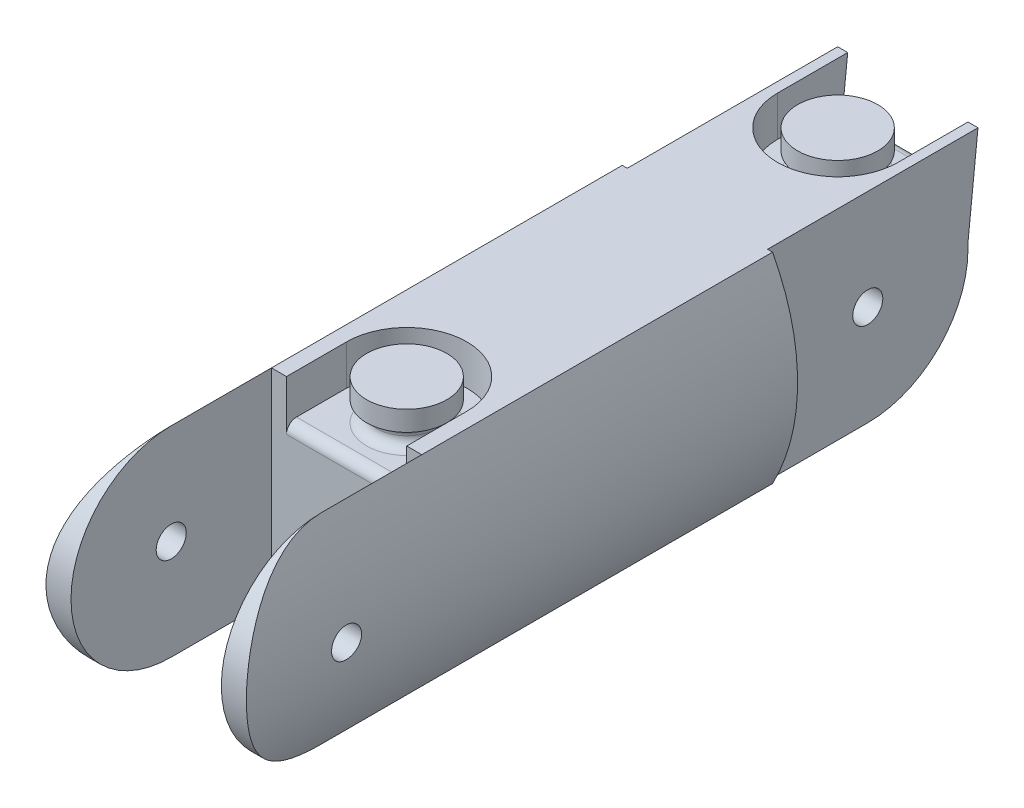
SolidWorks part; units mm, degrees
ref_plane "Alzado" through (0, 0, 0) normal (0, 0, 1) x (1, 0, 0)
ref_plane "Planta" through (0, 0, 0) normal (0, 1, 0) x (1, 0, 0)
ref_plane "Vista lateral" through (0, 0, 0) normal (1, 0, 0) x (0, 0, -1)
sketch "Croquis2" plane through (0, 0, 0) normal (0, 0, 1) x (1, 0, 0)
  line L5 (-7.5, -10) -> (7.5, -10)
  line L7 (-7.5, 10) -> (7.5, 10)
  line L9 (-7.5, -10) -> (7.5, 10) construction
  line L10 (-7.5, 10) -> (7.5, -10) construction
  arc A2 (-7.5, 10) -> (-7.5, -10) centre (11.25, 0) ccw
  arc A3 (7.5, -10) -> (7.5, 10) centre (-11.25, 0) ccw
  point P0 (0, 0)
  dimension "D1" = 15
  dimension "D2" = 20
extrude "Saliente-Extruir2" add sketch "Croquis2" along normal blind 55
sketch "Croquis4" plane through (0, 0, 0) normal (0, 0, -1) x (-1, 0, 0)
  line L1 (7.5, -10) -> (-7.5, -10) construction
  circle A0 centre (0, -7) radius 1.5
  dimension "D2" = 3
  dimension "D1" = 3
extrude "Cortar-Extruir1" cut sketch "Croquis4" against normal blind 50
sketch "Croquis3" plane through (0, 0, 0) normal (0, 0, -1) x (-1, 0, 0)
  line L8 (7.5, -10) -> (-7.5, -10) construction
  line L10 (7, 10) -> (7, -10)
  line L11 (7, -10) -> (3, -10)
  line L12 (-7, 10) -> (-7, -10)
  line L13 (7, 10) -> (-7, -10) construction
  line L14 (7, -10) -> (-7, 10) construction
  line L16 (3, -3) -> (3, -10)
  line L17 (-3, -10) -> (-7, -10)
  line L19 (-3, -3) -> (3, -3)
  line L20 (-3, -3) -> (-3, -10)
  line L21 (-7, 10) -> (7, 10)
  point P0 (0, 0)
  dimension "D1" = 14
  dimension "D2" = 4
  dimension "D3" = 4
  dimension "D4" = 7
extrude "Saliente-Extruir3" add sketch "Croquis3" along normal blind 20
sketch "Croquis8" plane through (-7, 0, 0) normal (-1, 0, 0) x (0, 0, 1)
  line L0 (-20, -10) -> (-20, 10) construction
  line L1 (-20, -10) -> (0, -10) construction
  circle A0 centre (-10, 0) radius 1.5
  point P4 (-20, 0)
  dimension "D1" = 3
  dimension "D2" = 10
  dimension "D3" = 10
extrude "Cortar-Extruir4" cut sketch "Croquis8" against normal blind 14
fillet "Redondeo1" radius 10 2 edges at (-5, -10, -20) (5, -10, -20)
sketch "Croquis6" plane through (0, 0, 55) normal (0, 0, 1) x (1, 0, 0)
  line L1 (-7.5, 10) -> (7.5, 10)
  line L2 (-7.5, 10) -> (-7.5, -10)
  line L3 (-7.5, -10) -> (7.5, -10)
  line L4 (7.5, 10) -> (7.5, -10)
extrude "Cortar-Extruir2" cut sketch "Croquis6" against normal blind 20
sketch "Croquis7" plane through (0, 0, 0) normal (1, 0, 0) x (0, 0, -1)
  line L0 (-55, 10) -> (-55, -10) construction
  line L2 (-45, -10) -> (-60, -10)
  line L4 (-45, 10) -> (-60, 10)
  line L5 (-60, -10) -> (-60, 10)
  arc A0 (-45, 10) -> (-45, -10) centre (-45, 0) ccw
  circle A1 centre (-45, 0) radius 1.5
  dimension "D3" = 10
  dimension "D4" = 3
  dimension "D1" = 10
  dimension "D2" = 15
  dimension "D5" = 20
extrude "Cortar-Extruir3" cut sketch "Croquis7" against normal through all both and the other way through all
sketch "Sketch1" plane through (0, 10, 0) normal (0, 1, 0) x (1, 0, 0)
  line L0 (7.5, -35) -> (-7.5, -35) construction
  line L1 (-7, 20) -> (7, 20) construction
  line L4 (-6, 14) -> (-6, 20)
  line L5 (-6, 20) -> (6, 20)
  line L6 (6, 14) -> (6, 20)
  line L8 (-6, -29) -> (-6, -35)
  line L9 (-6, -35) -> (6, -35)
  line L10 (6, -29) -> (6, -35)
  arc A0 (-6, 14) -> (6, 14) centre (0, 14) ccw
  arc A1 (6, -29) -> (-6, -29) centre (0, -29) ccw
  dimension "D1" = 12
  dimension "D2" = 12
  dimension "D3" = 6
  dimension "D4" = 6
extrude "Cut-Extrude1" cut sketch "Sketch1" against normal blind 4
sketch "Sketch2" plane through (0, 6, 0) normal (0, 1, 0) x (1, 0, 0)
  circle A0 centre (0, -29) radius 3
  circle A1 centre (0, 14) radius 3
  dimension "D1" = 6
  dimension "D2" = 6
extrude "Boss-Extrude1" add sketch "Sketch2" along normal blind 2
sketch "Sketch3" plane through (0, 8, 0) normal (0, 1, 0) x (1, 0, 0)
  circle A0 centre (0, 14) radius 4
  circle A1 centre (0, -29) radius 4
  dimension "D1" = 8
  dimension "D2" = 8
extrude "Boss-Extrude2" add sketch "Sketch3" along normal blind 2
fillet "Fillet1" radius 1 4 edges at (0, 8, -11) (0, 6, -11) (0, 8, 32) (0, 6, 32)
fillet "Fillet2" radius 1 2 edges at (0, 6, 35) (0, 6, -20)
fillet "Fillet3" radius 1 2 edges at (-1.5, -7, 0) (1.5, -7, 35)
sketch "Sketch4" plane through (7, 0, 0) normal (1, 0, 0) x (0, 0, -1)
  line L0 (20, 10) -> (21, 10)
  line L1 (21, 10) -> (19.666, -2.5629)
  line L2 (19.666, -2.5629) -> (20, 10)
  arc A0 (10, -10) -> (20, 0) centre (10, 0) ccw construction
  dimension "D1" = 1
sketch "Sketch5" plane through (-7, 0, 0) normal (-1, 0, 0) x (0, 0, 1)
  line L0 (-20, 10) -> (-21, 10)
  line L1 (-21, 10) -> (-19.666, -2.5629)
  line L2 (-19.666, -2.5629) -> (-20, 10)
extrude "Boss-Extrude3" add sketch "Sketch4" against normal blind 1
extrude "Boss-Extrude4" add sketch "Sketch5" against normal blind 1
sketch "Sketch6" plane through (0, 0, 0) normal (0, 0, -1) x (-1, 0, 0)
  line L0 (-7, 10) -> (-7, -10) construction
  line L1 (-3, -4) -> (3, -4)
  line L2 (-3, -2) -> (3, -2)
  line L3 (7, -10) -> (3, -10) construction
  arc A0 (-3, -2) -> (-3, -4) centre (-3, -3) ccw
  arc A1 (3, -4) -> (3, -2) centre (3, -3) ccw
  dimension "D1" = 2
  dimension "D2" = 2
  dimension "D3" = 6
  dimension "D4" = 4
  dimension "D5" = 8
extrude "Cut-Extrude3" cut sketch "Sketch6" along normal blind 50 from offset 28 offset against normal yes
sketch "Sketch7" plane through (0, -10, 0) normal (0, -1, 0) x (1, 0, 0)
  line L0 (7, -20) -> (-7, -20) construction
  line L1 (-4, 0) -> (4, 0)
  line L2 (-4, 0) -> (-4, -20)
  line L3 (-4, -20) -> (4, -20)
  line L4 (4, 0) -> (4, -20)
  line L5 (-7, -10) -> (-7, -20) construction
  dimension "D1" = 8
  dimension "D2" = 3
extrude "Cut-Extrude4" cut sketch "Sketch7" against normal blind 7
fillet "Fillet4" radius 0.5 3 edges at (3.7071, -3.7071, 0) (-3.7071, -3.7071, 0) (0, -4, 0)
